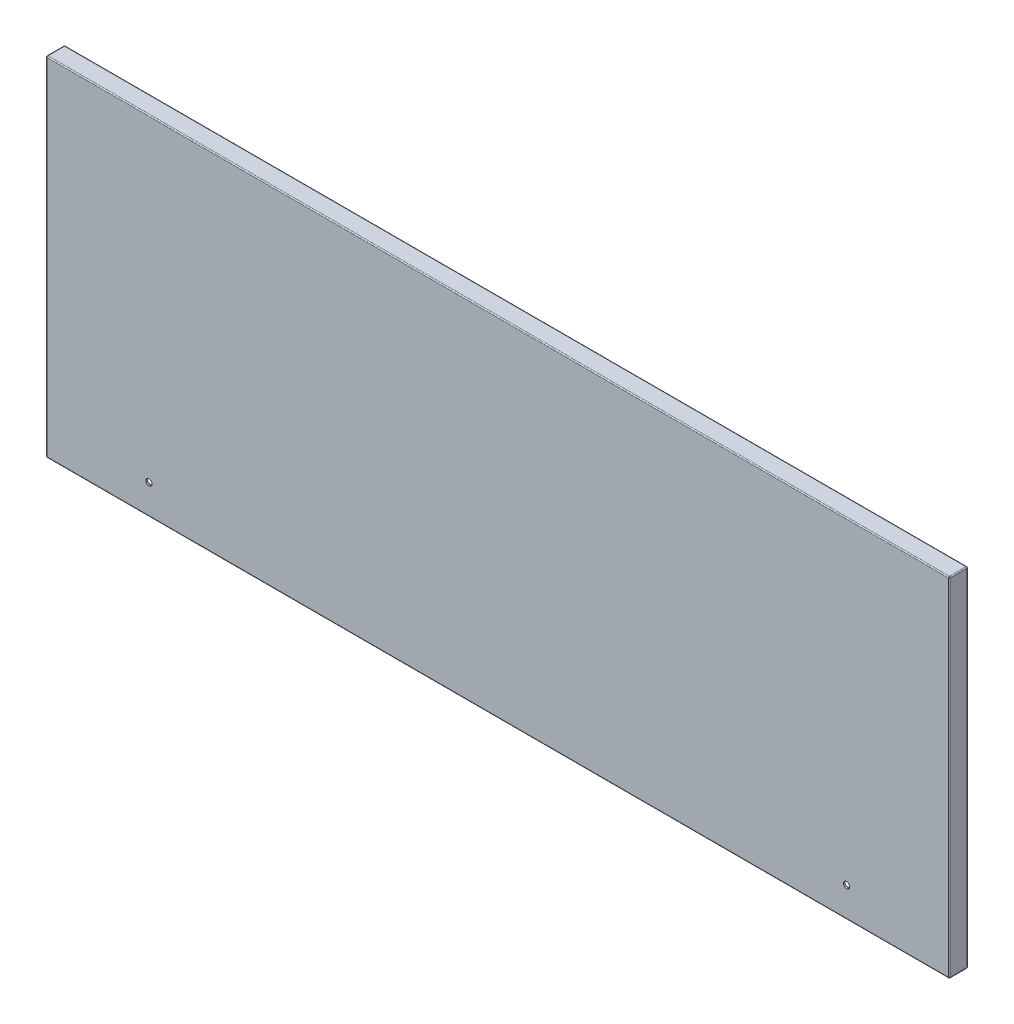
SolidWorks part; units mm, degrees
ref_plane "前视基准面" through (0, 0, 0) normal (0, 0, 1) x (1, 0, 0)
ref_plane "上视基准面" through (0, 0, 0) normal (0, 1, 0) x (1, 0, 0)
ref_plane "右视基准面" through (0, 0, 0) normal (1, 0, 0) x (0, 0, -1)
sketch "草图1" plane through (0, 0, 0) normal (0, 0, 1) x (1, 0, 0)
  line L1 (439, -169) -> (-439, -169)
  line L2 (439, -169) -> (439, 169)
  line L3 (439, 169) -> (-439, 169)
  line L4 (-439, -169) -> (-439, 169)
  line L5 (439, -169) -> (-439, 169) construction
  line L6 (439, 169) -> (-439, -169) construction
  point P0 (0, 0)
  dimension "D1" = 878
  dimension "D2" = 338
extrude "凸台-拉伸1" add sketch "草图1" along normal blind 1.5
sketch "草图2" plane through (0, 0, 0) normal (0, 0, -1) x (-1, 0, 0)
  line L1 (-439, -169) -> (439, -169)
  line L2 (-439, -169) -> (-439, 169)
  line L3 (-439, 169) -> (439, 169)
  line L4 (439, -169) -> (439, 169)
  line L5 (-439, -169) -> (439, 169) construction
  line L6 (-439, 169) -> (439, -169) construction
  line L7 (-437.5, -167.5) -> (437.5, -167.5)
  line L8 (-437.5, -167.5) -> (-437.5, 167.5)
  line L9 (-437.5, 167.5) -> (437.5, 167.5)
  line L10 (437.5, -167.5) -> (437.5, 167.5)
  line L11 (-437.5, -167.5) -> (437.5, 167.5) construction
  line L12 (-437.5, 167.5) -> (437.5, -167.5) construction
  point P0 (0, 0)
  point P7 (0, 0)
  dimension "D1" = 1.5
  dimension "D2" = 1.5
extrude "凸台-拉伸2" add sketch "草图2" along normal blind 15
sketch "草图3" plane through (0, 0, -15) normal (0, 0, -1) x (-1, 0, 0)
  line L1 (-439, -169) -> (439, -169)
  line L2 (-439, -169) -> (-439, 169)
  line L3 (-439, 169) -> (439, 169)
  line L4 (439, -169) -> (439, 169)
  line L5 (-439, -169) -> (439, 169) construction
  line L6 (-439, 169) -> (439, -169) construction
  line L7 (-424, -159) -> (424, -159)
  line L8 (-424, -159) -> (-424, 159)
  line L9 (-424, 159) -> (424, 159)
  line L10 (424, -159) -> (424, 159)
  line L11 (-424, -159) -> (424, 159) construction
  line L12 (-424, 159) -> (424, -159) construction
  point P0 (0, 0)
  point P7 (0, 0)
  dimension "D1" = 10
  dimension "D2" = 15
extrude "凸台-拉伸3" add sketch "草图3" along normal blind 1.5
sketch "草图6" plane through (0, 0, 1.5) normal (0, 0, 1) x (1, 0, 0)
  line L0 (0, -169) -> (0, 169) construction
  line L1 (-439, -169) -> (439, -169) construction
  line L2 (439, 169) -> (-439, 169) construction
  line L3 (-439, 169) -> (-439, -169) construction
  circle A0 centre (-339, -140) radius 3
  circle A1 centre (339, -140) radius 3
  dimension "D3" = 6
  dimension "D1" = 100
  dimension "D2" = 29
extrude "切除-拉伸1" cut sketch "草图6" against normal through all
fillet "圆角1" radius 1 12 edges at (0, -169, -16.5) (439, 0, -16.5) (0, 169, -16.5) (-439, 169, -7.5) (-439, 0, -16.5) (439, -169, -7.5) (-439, -169, -7.5) (-439, 0, 1.5) (0, -169, 1.5) (0, 169, 1.5) (439, 0, 1.5) (439, 169, -7.5)
sketch "草图8" plane through (0, 0, 1.5) normal (0, 0, 1) x (1, 0, 0)
  line L0 (100, 199) -> (100, 187) construction
  line L1 (125.202, 187) -> (74.798, 187)
  line L2 (-438, 169) -> (438, 169) construction
  line L3 (135, 199) -> (65, 199)
  line L4 (0, -403.0133) -> (0, 168) construction
  line L5 (132.0982, 189.7582) -> (65, 199) construction
  line L6 (135, 199) -> (67.9018, 189.7582) construction
  line L7 (438, 168) -> (-438, 168) construction
  arc A0 (65, 199) -> (74.798, 187) centre (74.798, 197) ccw
  arc A1 (135, 199) -> (125.202, 187) centre (125.202, 197) cw
  point P0 (100, 194.1793)
  dimension "D3" = 10
  dimension "D1" = 70
  dimension "D2" = 12
  dimension "D4" = 30
  dimension "D5" = 100
sketch "草图9" plane through (0, -159, 0) normal (0, 1, 0) x (1, 0, 0)
  line L0 (15, 0) -> (15, 16.5)
  line L1 (424, 16.5) -> (-424, 16.5) construction
  line L2 (15, 16.5) -> (-15, 16.5)
  line L3 (-15, 16.5) -> (-15, 0)
  line L4 (-15, 0) -> (-13.5, 0)
  line L5 (-13.5, 0) -> (-13.5, 15)
  line L6 (424, 15) -> (-424, 15) construction
  line L7 (-13.5, 15) -> (13.5, 15)
  line L8 (13.5, 15) -> (13.5, 0)
  line L9 (13.5, 0) -> (15, 0)
  line L10 (0, 0) -> (0, -559.5718) construction
  dimension "D1" = 1.5
  dimension "D2" = 1.5
  dimension "D3" = 16.5
  dimension "D4" = 30
  dimension "D5" = 16.5
extrude "凸台-拉伸5" add sketch "草图9" along normal up to next
fillet "圆角2" radius 2 2 edges at (-15, 0, -16.5) (15, 0, -16.5)
